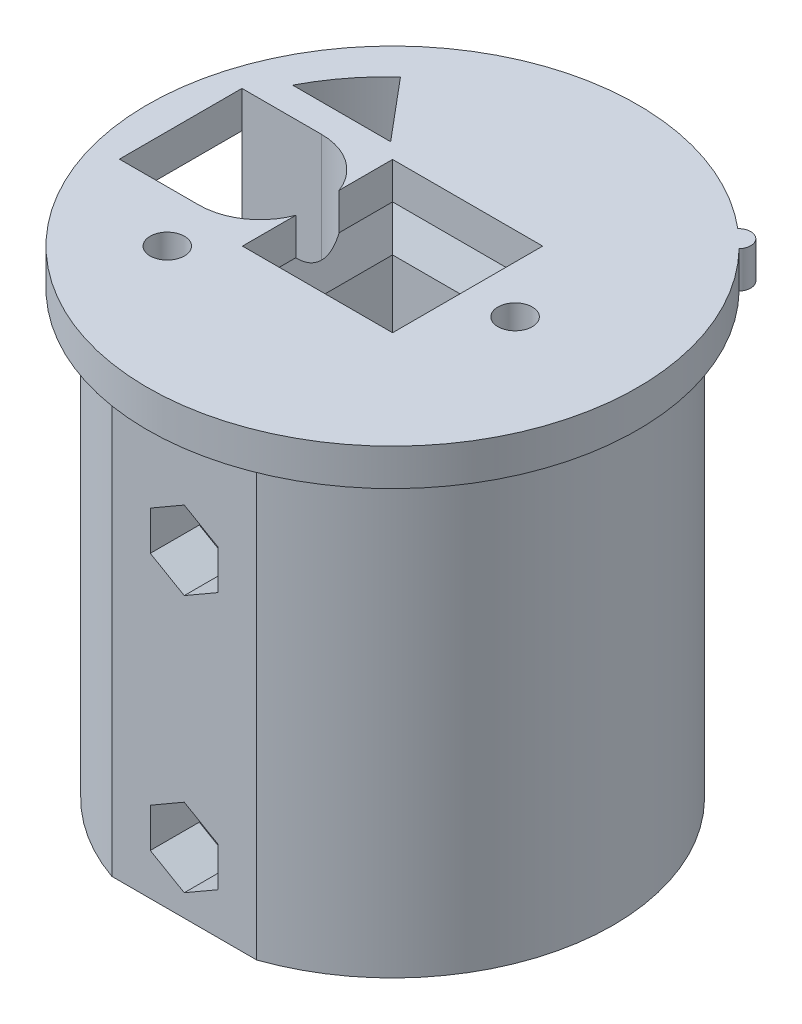
SolidWorks part; units mm, degrees
ref_plane "Спереди" through (0, 0, 0) normal (0, 0, 1) x (1, 0, 0)
ref_plane "Сверху" through (0, 0, 0) normal (0, 1, 0) x (1, 0, 0)
ref_plane "Справа" through (0, 0, 0) normal (1, 0, 0) x (0, 0, -1)
sketch "Sketch1" plane through (0, 0, 0) normal (0, 1, 0) x (1, 0, 0)
  line L0 (-5.125, 0) -> (-18, 0) construction
  line L1 (5.125, -5.125) -> (-5.125, -5.125)
  line L2 (5.125, -5.125) -> (5.125, 5.125)
  line L3 (5.125, 5.125) -> (-5.125, 5.125)
  line L4 (-5.125, -5.125) -> (-5.125, 5.125)
  line L5 (5.125, -5.125) -> (-5.125, 5.125) construction
  line L6 (5.125, 5.125) -> (-5.125, -5.125) construction
  circle A0 centre (0, 0) radius 18
  circle A1 centre (-12, 0) radius 2
  dimension "D1" = 36
  dimension "D3" = 6
  dimension "D2" = 10.25
extrude "Boss-Extrude1" add sketch "Sketch1" along normal blind 36
sketch "Sketch2" plane through (0, 36, 0) normal (0, 1, 0) x (1, 0, 0)
  line L0 (-10.8, 5) -> (-17.2916, 5)
  line L1 (-10.8, -5) -> (-17.2916, -5)
  line L2 (-5.125, 0) -> (-18, 0) construction
  line L3 (-5.125, 5.125) -> (-5.125, -5.125) construction
  circle A1 centre (0, 0) radius 18 construction
  arc A2 (-17.2916, 5) -> (-17.2916, -5) centre (0, 0) ccw
  arc A3 (-10.8, 5) -> (-10.8, -5) centre (-10.8, 0) cw
  point P12 (-5.8, 0)
  dimension "D1" = 5
extrude "Cut-Extrude1" cut sketch "Sketch2" against normal blind 7
sketch "Sketch4" plane through (0, 0, 0) normal (0, -1, 0) x (-1, 0, 0)
  line L0 (0, 0) -> (18, 21.4516) construction
  line L1 (0, 0) -> (18, -21.4516) construction
  line L2 (18, 21.4516) -> (18, -21.4516) construction
  line L3 (0, 0) -> (13.6996, 11.6756) construction
  line L4 (0, 0) -> (13.6996, -11.6756) construction
  line L5 (0, 0) -> (18, 0) construction
  line L6 (5.125, 5.125) -> (5.125, -5.125) construction
  line L7 (11.5702, 13.7888) -> (5.1423, 6.1284) construction
  line L8 (5.1423, 6.1284) -> (5.1423, -4.3826) construction
  line L9 (5.1423, -4.3826) -> (13.6996, -11.6756) construction
  line L10 (5.1423, 0.8729) -> (18.1354, 0.8729) construction
  line L12 (15.8104, 5.5479) -> (6.4604, 5.5479)
  line L13 (15.8104, 5.5479) -> (15.8104, -3.8021)
  line L14 (15.8104, -3.8021) -> (6.4604, -3.8021)
  line L15 (6.4604, 5.5479) -> (6.4604, -3.8021)
  line L16 (15.8104, 5.5479) -> (6.4604, -3.8021) construction
  line L17 (15.8104, -3.8021) -> (6.4604, 5.5479) construction
  arc A0 (13.6996, -11.6756) -> (11.5702, 13.7888) centre (0.5154, 0.0431) ccw construction
  circle A2 centre (0, 0) radius 18 construction
  point P2 (11, 0)
  point P5 (11.5702, 13.7888)
  point P7 (4.1157, 3.5076)
  point P8 (11.5702, -13.7888)
  point P11 (5.125, -6.1077)
  point P16 (11.1354, 0.8729)
  dimension "D5" = 10
  dimension "D1" = 100
  dimension "D2" = 3
  dimension "D3" = 3
  dimension "D4" = 9.35
  dimension "D6" = 7
extrude "Cut-Extrude3" cut sketch "Sketch4" against normal blind 20.4
sketch "Sketch5" plane through (0, 36, 0) normal (0, 1, 0) x (1, 0, 0)
  line L0 (0, 18) -> (0, -18) construction
  line L1 (5.9161, 17) -> (-5.9161, 17)
  line L2 (5.9161, -17) -> (-5.9161, -17)
  circle A0 centre (0, 0) radius 18 construction
  arc A1 (5.9161, 17) -> (-5.9161, 17) centre (0, 0) ccw
  arc A2 (5.9161, -17) -> (-5.9161, -17) centre (0, 0) cw
  point P11 (0, 17)
  dimension "D1" = 1
extrude "Cut-Extrude4" cut sketch "Sketch5" against normal blind 40
sketch "Sketch6" plane through (0, 0, -17) normal (0, 0, -1) x (-1, 0, 0)
  line L0 (0, 36) -> (0, 0) construction
  line L1 (5.9161, 36) -> (-5.9161, 36) construction
  line L3 (5.9161, 0) -> (-5.9161, 0) construction
  circle A0 centre (0, 26) radius 1.5
  circle A1 centre (0, 5) radius 1.5
  dimension "D1" = 3
  dimension "D2" = 10
  dimension "D3" = 5
extrude "Cut-Extrude5" cut sketch "Sketch6" against normal through all
sketch "Sketch7" plane through (0, 0, -17) normal (0, 0, -1) x (-1, 0, 0)
  circle A0 centre (0, 26) radius 3
  circle A1 centre (0, 5) radius 3
  dimension "D1" = 6
extrude "Cut-Extrude6" cut sketch "Sketch7" against normal blind 3
sketch "Sketch8" plane through (0, 0, 17) normal (0, 0, 1) x (1, 0, 0)
  line L0 (5.9161, 0) -> (5.9161, 36) construction
  line L1 (0, 22.8) -> (2.7713, 24.4)
  line L2 (2.7713, 24.4) -> (2.7713, 27.6)
  line L3 (2.7713, 27.6) -> (0, 29.2)
  line L4 (0, 29.2) -> (-2.7713, 27.6)
  line L5 (-2.7713, 27.6) -> (-2.7713, 24.4)
  line L6 (-2.7713, 24.4) -> (0, 22.8)
  line L9 (0, 1.8) -> (2.7713, 3.4)
  line L10 (2.7713, 3.4) -> (2.7713, 6.6)
  line L11 (2.7713, 6.6) -> (0, 8.2)
  line L12 (0, 8.2) -> (-2.7713, 6.6)
  line L13 (-2.7713, 6.6) -> (-2.7713, 3.4)
  line L14 (-2.7713, 3.4) -> (0, 1.8)
  circle A0 centre (0, 26) radius 3.2 construction
  circle A1 centre (0, 5) radius 3.2 construction
  dimension "D1" = 6.4
extrude "Cut-Extrude7" cut sketch "Sketch8" against normal blind 4
chamfer "Chamfer1" distance 1 angle 70 4 edges at (-5.125, 36, 0) (0, 36, -5.125) (0, 36, 5.125) (5.125, 36, 0) first distance on face at (-5.2523, 36, 0)
sketch "Sketch9" plane through (0, 0, 0) normal (0, -1, 0) x (1, 0, 0)
  line L0 (16.4542, -7.2979) -> (-16.4542, -7.2979) construction
  line L1 (-15.8104, -5.5479) -> (-6.4604, -5.5479) construction
  line L2 (-7.4542, -7.2979) -> (-15.4542, -7.2979)
  line L3 (-7.4542, -7.2979) -> (-11.6323, -12.2772)
  line L4 (5.125, -5.125) -> (-5.125, -5.125) construction
  circle A0 centre (0, 0) radius 18 construction
  arc A1 (-15.4542, -7.2979) -> (-11.6323, -12.2772) centre (0.5168, 1.0043) ccw
  point P10 (-11.4542, -7.2979)
  dimension "D8" = 18
  dimension "D1" = 1.75
  dimension "D2" = 5
  dimension "D3" = 6.5
  dimension "D4" = 50
  dimension "D5" = 8
  dimension "D6" = 2.1729
  dimension "D7" = 23.9084
extrude "Cut-Extrude8" cut sketch "Sketch9" against normal through all
sketch "Sketch12" plane through (0, 36, 0) normal (0, 1, 0) x (1, 0, 0)
  line L0 (18, 0) -> (-10.8, 0) construction
  line L1 (0, 0) -> (-12.7279, -12.7279) construction
  arc A0 (5.9161, -17) -> (5.9161, 17) centre (0, 0) ccw construction
  arc A1 (-17.2916, -5) -> (-5.9161, -17) centre (0, 0) ccw construction
  circle A2 centre (10, 0) radius 1.4
  circle A3 centre (-9.1924, -9.1924) radius 1.4
  dimension "D1" = 2.8
  dimension "D2" = 10
  dimension "D3" = 13
extrude "Cut-Extrude10" cut sketch "Sketch12" against normal blind 20
sketch "Sketch13" plane through (0, 36, 0) normal (0, 1, 0) x (1, 0, 0)
  line L0 (-10.8, 5) -> (-17.2916, 5)
  line L1 (-6.125, 6.125) -> (6.125, 6.125)
  line L2 (-7.4542, 7.2979) -> (-15.4542, 7.2979)
  line L3 (-6.125, -6.125) -> (6.125, -6.125)
  line L4 (6.125, 6.125) -> (6.125, -6.125)
  line L5 (-6.125, 6.125) -> (6.125, -6.125) construction
  line L6 (-6.125, -6.125) -> (6.125, 6.125) construction
  line L7 (-17.2916, -5) -> (-10.8, -5)
  line L8 (-17.2916, 5) -> (-17.2916, -5)
  line L9 (-6.125, 1.7732) -> (-6.125, 6.125)
  line L10 (-6.125, -1.7732) -> (-6.125, -6.125)
  line L11 (-7.4542, 7.2979) -> (-11.6323, 12.2772)
  circle A0 centre (0, 0) radius 20
  arc A1 (-10.8, 5) -> (-6.125, 1.7732) centre (-10.8, 0) cw
  arc A2 (-6.125, -1.7732) -> (-10.8, -5) centre (-10.8, 0) cw
  circle A3 centre (10, 0) radius 1.4
  circle A4 centre (-9.1924, -9.1924) radius 1.4
  arc A5 (-11.6323, 12.2772) -> (-15.4542, 7.2979) centre (0.5168, -1.0043) ccw
  dimension "D1" = 40
extrude "Boss-Extrude2" add sketch "Sketch13" along normal blind 3
sketch "Sketch14" plane through (0, 39, 0) normal (0, 1, 0) x (1, 0, 0)
  line L0 (0, 0) -> (0, 20) construction
  line L1 (0, 0) -> (12.8558, 15.3209) construction
  line L2 (12.8558, 15.3209) -> (14.3216, 13.9603)
  circle A0 centre (0, 0) radius 20 construction
  arc A1 (12.8558, 15.3209) -> (14.3216, 13.9603) centre (13.5887, 14.6406) cw
  dimension "D2" = 1
  dimension "D1" = 40
  dimension "D3" = 2
extrude "Boss-Extrude3" add sketch "Sketch14" against normal up to surface (3 mm away) up to face at (0, 36, 20)
